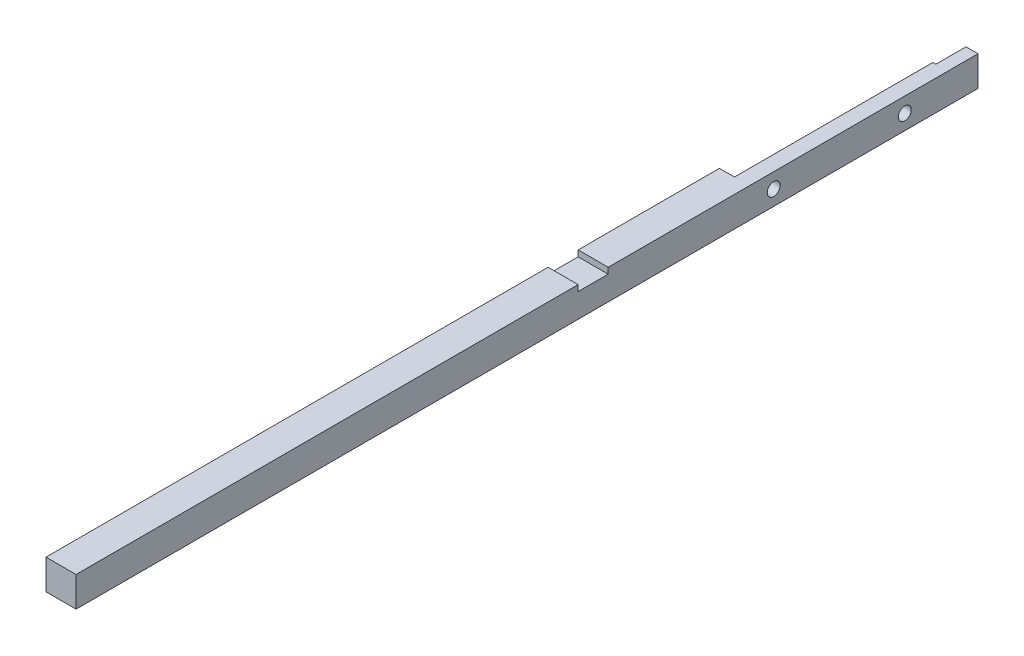
SolidWorks part; units mm, degrees
ref_plane "Plan de face" through (0, 0, 0) normal (0, 0, 1) x (1, 0, 0)
ref_plane "Plan de dessus" through (0, 0, 0) normal (0, 1, 0) x (1, 0, 0)
ref_plane "Plan de droite" through (0, 0, 0) normal (1, 0, 0) x (0, 0, -1)
sketch "Esquisse1" plane through (0, 0, 0) normal (0, 0, 1) x (1, 0, 0)
  line L0 (-5, 5) -> (5, -5) construction
  line L1 (-5, 5) -> (5, 5)
  line L2 (-5, 5) -> (-5, -5)
  line L3 (-5, -5) -> (5, -5)
  line L4 (5, 5) -> (5, -5)
  dimension "D1" = 10
extrude "Boss.-Extru.1" add sketch "Esquisse1" along normal offset from surface (307 mm away) 2 offset beyond the face yes
sketch "Esquisse2" plane through (0, 0, 0) normal (0, 1, 0) x (1, 0, 0)
  line L0 (-5, -83.0125) -> (0, -83.0125)
  line L1 (0, -83.0125) -> (0, -7)
  line L2 (0, -7) -> (5, -7)
  line L3 (5, -7) -> (5, 0)
  line L4 (5, 0) -> (-5, 0)
  line L5 (-5, 0) -> (-5, -83.0125)
  line L6 (5, -307) -> (5, 0) construction
  line L7 (-5, -307) -> (-5, 0) construction
  line L8 (-14, -82.0125) -> (0, -82.0125) construction
  dimension "D1" = 1
  dimension "D2" = 7
extrude "Enlèv. mat.-Extru.1" cut sketch "Esquisse2" against normal through all and the other way through all
sketch "Esquisse4" plane through (5, 0, 0) normal (1, 0, 0) x (0, 0, -1)
  line L0 (-140, 239) -> (-140, 3) construction
  line L1 (-140, 5) -> (-130, 5)
  line L2 (-140, 5) -> (-140, 3)
  line L3 (-140, 3) -> (-130, 3)
  line L4 (-130, 5) -> (-130, 3)
  line L5 (-130, 239) -> (-130, 3) construction
  line L6 (-307, 5) -> (-7, 5) construction
  dimension "D1" = 2
extrude "Enlèv. mat.-Extru.3" cut sketch "Esquisse4" against normal through all
sketch "Esquisse5" plane through (5, 0, 0) normal (1, 0, 0) x (0, 0, -1)
  line L0 (-307, -5) -> (-7, -5) construction
  line L1 (-130, -5) -> (-140, -5)
  line L2 (-130, -5) -> (-130, -3)
  line L3 (-130, -3) -> (-140, -3)
  line L4 (-140, -5) -> (-140, -3)
  line L7 (-140, 3) -> (-140, 239) construction
  line L8 (-130, 3) -> (-130, 239) construction
  dimension "D1" = 2
extrude "Enlèv. mat.-Extru.4" [suppressed] cut sketch "Esquisse5" against normal through all
sketch "Esquisse6" plane through (0, 0, 0) normal (-1, 0, 0) x (0, 0, 1)
  line L0 (83.0125, 5) -> (7, 5) construction
  line L1 (7, -5) -> (17, -5)
  line L2 (7, -5) -> (7, 5)
  line L3 (7, 5) -> (17, 5)
  line L4 (17, -5) -> (17, 5)
  dimension "D1" = 10
extrude "Enlèv. mat.-Extru.5" cut sketch "Esquisse6" against normal blind 1
hole_wizard "Dégagement M41" positions "Esquisse8" profile "Esquisse9" hole size "M4" standard "Ansi Metric" end condition through all
sketch "Esquisse8" plane through (0, 0, 0) normal (-1, 0, 0) x (0, 0, 1)
  point P0 (74.9525, 0)
  point P5 (31.3525, 0)
sketch "Esquisse9" plane through (0, 0, 74.9525) normal (0, 1, 0) x (0, 0, 1)
  line L0 (0, 0) -> (0, 5)
  line L1 (0, 5) -> (2.15, 5)
  line L2 (2.15, 5) -> (2.15, 0)
  line L5 (2.15, 0) -> (0, 0)
  line L11 (0, -6.35) -> (0, 107.95) construction
  dimension "Diamètre du perçage jusqu'au prochain" = 4.3
  dimension "Profondeur du perçage jusqu'au prochain" = 5
